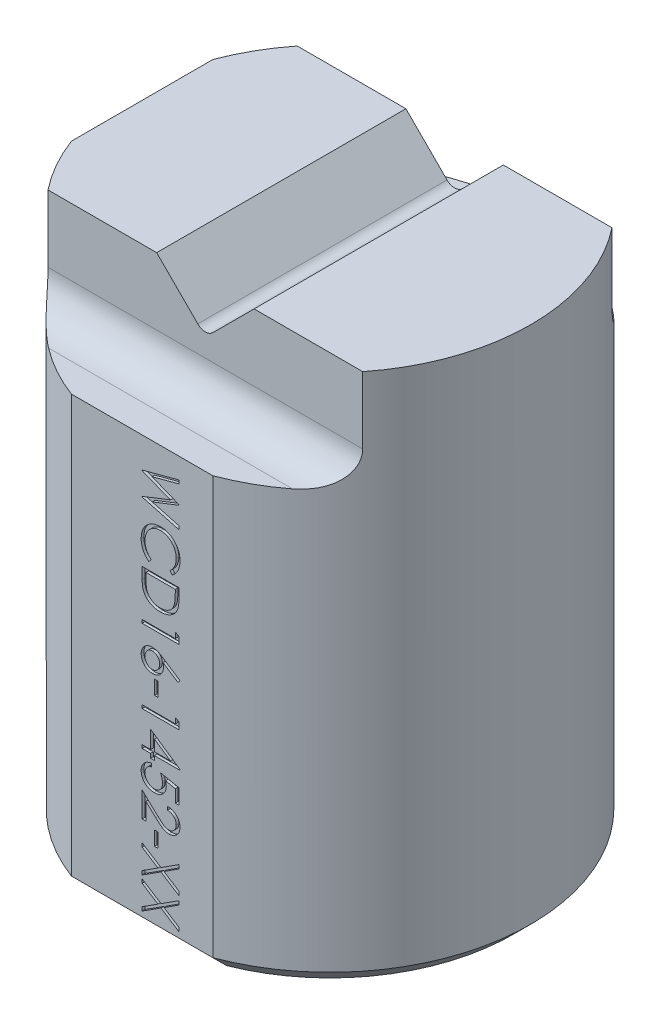
SolidWorks part; units mm, degrees
material "S7"
ref_plane "Alzado" through (0, 0, 0) normal (0, 0, 1) x (1, 0, 0)
ref_plane "Planta" through (0, 0, 0) normal (0, 1, 0) x (1, 0, 0)
ref_plane "Vista lateral" through (0, 0, 0) normal (1, 0, 0) x (0, 0, -1)
sketch "Croquis1" plane through (0, 0, 0) normal (0, 1, 0) x (1, 0, 0)
  circle A0 centre (0, 0) radius 19.0246
  dimension "D1" = 38.0492
extrude "Saliente-Extruir1" add sketch "Croquis1" along normal blind 50.8
sketch "Croquis12" plane through (0, 0, 0) normal (1, 0, 0) x (0, 0, -1)
  line L0 (11.811, 50.8) -> (19.0246, 50.8)
  line L2 (0, 50.8) -> (-11.811, 50.8) construction
  line L9 (-11.811, 50.8) -> (-19.0246, 50.8)
  line L10 (-11.811, 50.8) -> (-11.811, 44.45)
  line L11 (-15.113, 41.148) -> (-19.0246, 41.148)
  line L12 (-19.0246, 50.8) -> (-19.0246, 41.148)
  line L13 (19.0246, 50.8) -> (19.0246, 41.148)
  line L14 (0, 50.8) -> (0, 0) construction
  line L15 (19.0246, 50.8) -> (-19.0246, 50.8) construction
  line L16 (-19.0246, 50.8) -> (-19.0246, 0) construction
  line L17 (15.113, 41.148) -> (19.0246, 41.148)
  line L18 (11.811, 50.8) -> (11.811, 44.45)
  arc A0 (-11.811, 44.45) -> (-15.113, 41.148) centre (-15.113, 44.45) cw
  arc A2 (11.811, 44.45) -> (15.113, 41.148) centre (15.113, 44.45) ccw
  dimension "D3" = 3.302
  dimension "D1" = 9.652
  dimension "D2" = 23.622
extrude "Cortar-Extruir5" cut sketch "Croquis12" against normal blind 50.8 and the other way blind 50.8
sketch "Croquis14" plane through (0, 0, 0) normal (0, 0, 1) x (1, 0, 0)
  line L5 (-4.6159, 50.8) -> (-0.7184, 46.9026)
  line L10 (-14.9143, 50.8) -> (14.9143, 50.8) construction
  line L11 (0.7184, 46.9026) -> (4.6159, 50.8)
  line L12 (4.6159, 50.8) -> (-4.6159, 50.8)
  line L13 (0, 50.8) -> (0, 0) construction
  line L14 (-19.0246, 0) -> (19.0246, 0) construction
  arc A2 (-0.7184, 46.9026) -> (0.7184, 46.9026) centre (0, 47.621) ccw
  circle A3 centre (0, 50.8) radius 3.2639 construction
  point P13 (0, 47.6267)
  point P14 (-1.3913, 47.0218)
  point P15 (0, 0)
  point P16 (0.5253, 46.6364)
  point P17 (0.9734, 47.1155)
  point P18 (0, 0)
  point P19 (0, 0)
  point P20 (0, 0)
  point P21 (0, 0)
  point P22 (0, 48.2095)
  point P23 (0, 0)
  point P24 (0, 50.9566)
  point P25 (0, 0)
  point P26 (0, 50.8009)
  dimension "D1" = 9.2317
  dimension "D4" = 90
  dimension "D2" = 1.016
  dimension "D3" = 6.5278
extrude "Cortar-Extruir7" cut sketch "Croquis14" against normal blind 50.8 and the other way blind 50.8 contours L5 A2 L11 L12
sketch "Croquis11" plane through (0, 50.8, 0) normal (0, 1, 0) x (1, 0, 0)
  line L0 (-19.0246, 0) -> (-17.8054, 0) construction
  line L1 (0, -19.0246) -> (0, -17.8054) construction
  line L3 (-17.8054, 0) -> (-17.8054, 6.701)
  line L7 (-17.8054, 0) -> (-17.8054, -6.701)
  line L10 (-19.0246, 0) -> (19.0246, 0) construction
  line L11 (0, -17.8054) -> (-6.701, -17.8054)
  line L15 (0, -17.8054) -> (6.701, -17.8054)
  circle A0 centre (0, 0) radius 19.0246 construction
  arc A1 (-17.8054, -6.701) -> (-17.8054, 6.701) centre (0, 0) cw
  arc A2 (-6.701, -17.8054) -> (6.701, -17.8054) centre (0, 0) ccw
  arc A3 (-11.5556, -15.113) -> (11.5556, -15.113) centre (0, 0) ccw construction
  arc A4 (14.9143, -11.811) -> (14.9143, 11.811) centre (0, 0) ccw construction
  arc A5 (11.5556, 15.113) -> (-11.5556, 15.113) centre (0, 0) ccw construction
  point P24 (0, 19.0246)
  dimension "D1" = 36.83
  dimension "D2" = 36.83
extrude "Cortar-Extruir4" cut sketch "Croquis11" against normal blind 50.8
sketch "Croquis16" plane through (0, 0, 17.8054) normal (0, 0, 1) x (1, 0, 0)
  line L0 (0, 0) -> (0, 41.148) construction
  line L1 (11.5556, 41.148) -> (-11.5556, 41.148) construction
  text T0 "WCD16-1452-XX"
chamfer "Chaflán1" distance 1.5875 angle 45 4 edges at (0, 0, 17.8054) (13.4524, 0, -13.4524) (-17.8054, 0, 0) (-13.4524, 0, 13.4524)
extrude "Cortar-Extruir8" cut sketch "Croquis16" against normal blind 0.254
